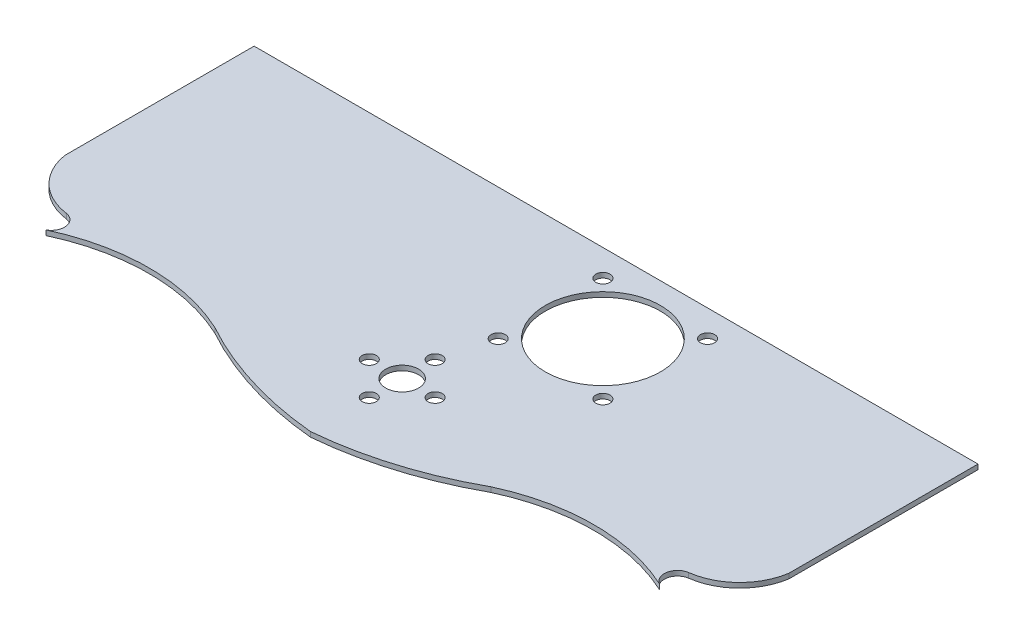
SolidWorks part; units mm, degrees
ref_plane "Front Plane" through (0, 0, 0) normal (0, 0, 1) x (1, 0, 0)
ref_plane "Top Plane" through (0, 0, 0) normal (0, 1, 0) x (1, 0, 0)
ref_plane "Right Plane" through (0, 0, 0) normal (1, 0, 0) x (0, 0, -1)
ref_plane "Plane1" through (0, 22.5, 0) normal (0, 1, 0) x (1, 0, 0)
ref_plane "Plane2" through (0, 24, 0) normal (0, 1, 0) x (1, 0, 0)
sketch "Sketch2" plane through (0, 22.5, 0) normal (0, 1, 0) x (1, 0, 0)
  line L0 (0, -100) -> (0, 70) construction
  line L15 (-34.8399, -30) -> (34.8399, -30) construction
  line L16 (-110, 50) -> (110, 50)
  line L17 (0, 50) -> (0, -30) construction
  line L19 (-110, 50) -> (-110, -7.5)
  line L21 (110, 50) -> (110, -7.5)
  arc A1 (94.5, -22.5368) -> (93.25, -30) centre (95.1559, -26.4829) ccw
  arc A3 (110, -7.5) -> (94.5, -22.5368) centre (92.222, -4.6815) cw
  arc A7 (93.25, -30) -> (41.9625, -30) centre (67.6063, -85.0296) ccw
  arc A9 (93.25, -30) -> (41.9625, -30) centre (67.6063, -85.0296) ccw construction
  arc A11 (41.9625, -30) -> (0, -42.8761) centre (-9.5248, 62.9793) cw
  circle A12 centre (20, 26) radius 17.5
  circle A13 centre (20, 26) radius 17.5 construction
  circle A14 centre (0, -15) radius 5
  circle A15 centre (0, -15) radius 5 construction
  arc A17 (0, -42.8761) -> (41.9625, -30) centre (-9.5248, 62.9793) ccw construction
  arc A18 (-41.9625, -30) -> (0, -42.8761) centre (9.5248, 62.9793) ccw
  arc A20 (-41.9625, -30) -> (0, -42.8761) centre (9.5248, 62.9793) ccw construction
  arc A22 (-41.9625, -30) -> (-93.25, -30) centre (-67.6063, -85.0296) ccw
  arc A24 (-41.9625, -30) -> (-93.25, -30) centre (-67.6063, -85.0296) ccw construction
  arc A25 (-110, -7.5) -> (-94.5, -22.5368) centre (-92.222, -4.6815) ccw
  arc A26 (-110, -7.5) -> (-94.5, -22.5368) centre (-92.222, -4.6815) ccw construction
  arc A27 (-94.5, -22.5368) -> (-93.25, -30) centre (-95.1559, -26.4829) cw
  arc A28 (-93.25, -30) -> (-94.5, -22.5368) centre (-95.1559, -26.4829) ccw construction
  point P0 (0, 10.0408)
extrude "Boss-Extrude2" add sketch "Sketch2" along normal up to surface (1.5 mm away) up to plane "Plane2"
hole_wizard "#6 Clearance Hole1" positions "Sketch5" profile "Sketch4" hole size "#6" standard "ANSI Inch" end condition through all
sketch "Sketch5" plane through (0, 24, 0) normal (0, 1, 0) x (1, 0, 0)
  point P0 (0, -5)
  point P3 (-10, -15)
  point P6 (10, -15)
  point P9 (0, -25)
  point P12 (4.0901, 41.9099)
  point P15 (35.9099, 41.9099)
  point P18 (35.9099, 10.0901)
  point P21 (4.0901, 10.0901)
sketch "Sketch4" plane through (0, 24, 5) normal (1, 0, 0) x (0, 0, 1)
  line L0 (0, 0) -> (0, 1.5)
  line L1 (0, 1.5) -> (2.159, 1.5)
  line L2 (2.159, 1.5) -> (2.159, 0)
  line L5 (2.159, 0) -> (0, 0)
  line L11 (0, -6.35) -> (0, 107.95) construction
  dimension "Thru Hole Dia." = 4.318
  dimension "Thru Hole Depth" = 1.5
